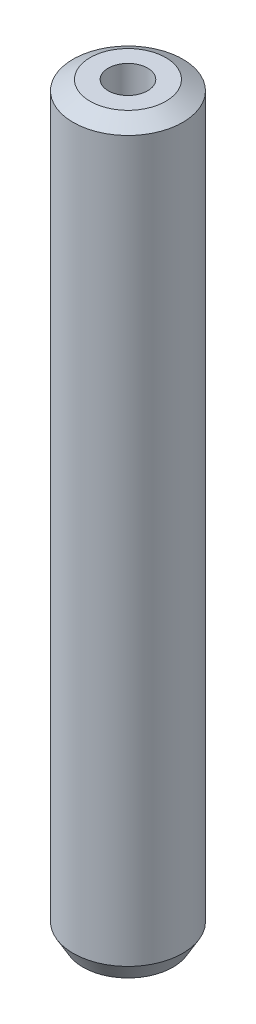
SolidWorks part; units mm, degrees
ref_plane "Front Plane" through (0, 0, 0) normal (0, 0, 1) x (1, 0, 0)
ref_plane "Top Plane" through (0, 0, 0) normal (0, 1, 0) x (1, 0, 0)
ref_plane "Right Plane" through (0, 0, 0) normal (1, 0, 0) x (0, 0, -1)
sketch "Sketch1" plane through (0, 0, 0) normal (0, 1, 0) x (1, 0, 0)
  circle A0 centre (0, 0) radius 10
  dimension "SHAFT_OD" = 20
extrude "Boss-Extrude1" add sketch "Sketch1" along normal blind 136.1598
sketch "Sketch2" plane through (0, 0, 0) normal (0, 1, 0) x (1, 0, 0)
  circle A0 centre (0, 0) radius 3.5912
  dimension "BORE_D" = 7.1824
extrude "Cut-Extrude1" cut sketch "Sketch2" along normal through all
chamfer "Chamfer1" distance 1.7866 angle 60 2 edges at (0, 136.1598, 10) (0, 0, 10) first distance on face at (0, 136.1598, 10) first distance on face at (0, 0, 3.5912)
